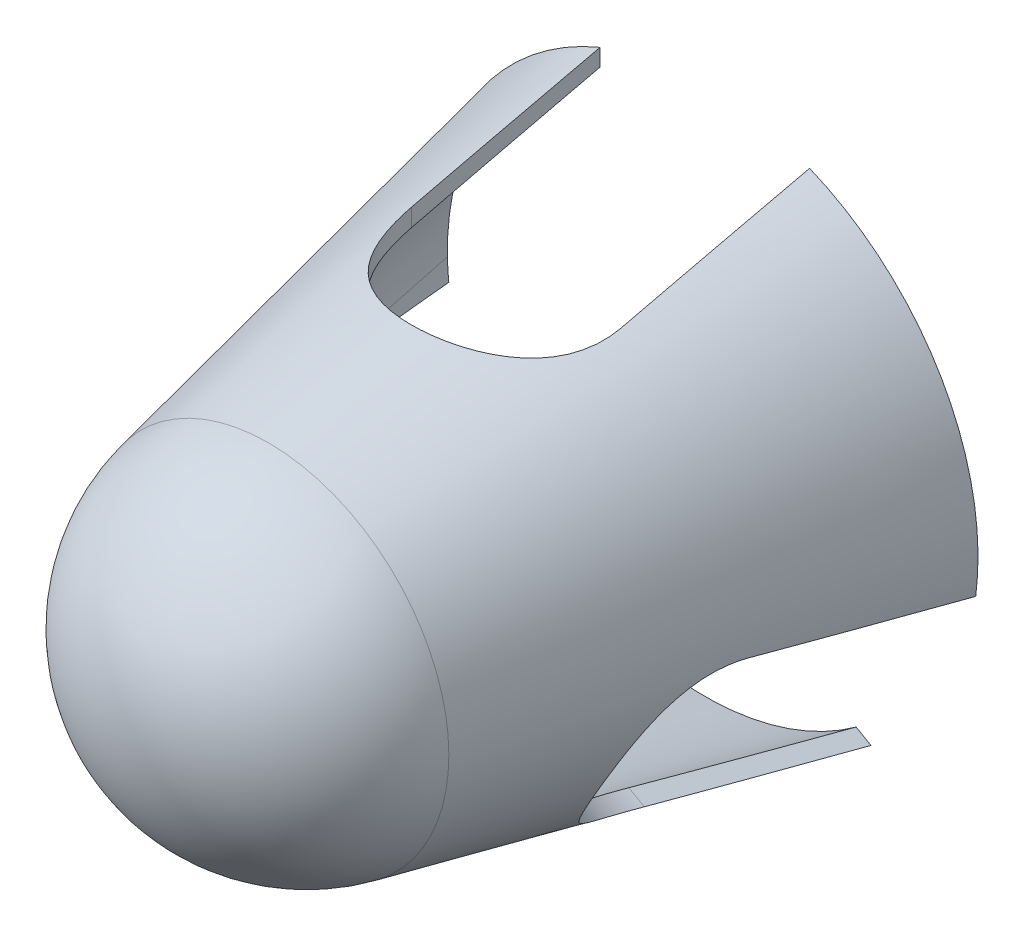
SolidWorks part; units mm, degrees
ref_plane "Ebene vorne" through (0, 0, 0) normal (0, 0, 1) x (1, 0, 0)
ref_plane "Ebene oben" through (0, 0, 0) normal (0, 1, 0) x (1, 0, 0)
ref_plane "Ebene rechts" through (0, 0, 0) normal (1, 0, 0) x (0, 0, -1)
sketch "Skizze1" plane through (0, 0, 0) normal (1, 0, 0) x (0, 0, -1)
  line L0 (900, -1303.8575) -> (900, 0) construction
  line L1 (-1000, 750) -> (1000, 750) construction
  line L2 (-1000, 750) -> (-1000, -750) construction
  line L3 (-1000, -750) -> (1000, -750) construction
  line L4 (1000, 750) -> (1000, -750) construction
  line L6 (900, -1303.8575) -> (-1183.0315, -861.0955)
  line L7 (-1000, 0) -> (-1000, -825)
  line L8 (-1000, -825) -> (900, -1228.8575)
  line L9 (0, 0) -> (-1960.7907, 0) construction
  line L10 (0, 0) -> (4818.5589, 0) construction
  line L11 (-1880.3328, 0) -> (-1000, 0)
  line L12 (900, -1228.8575) -> (900, -1303.8575)
  arc A1 (-1183.0315, -861.0955) -> (-1880.3328, 0) centre (-1000, 0) cw
  point P8 (0, 750)
  point P16 (1000, 0)
  dimension "D1" = 2000
  dimension "D2" = 1500
  dimension "D3" = 75
  dimension "D6" = 75
  dimension "D7" = 12
  dimension "D8" = 100
  dimension "D9" = 12
revolve "Rotation1" add sketch "Skizze1" angle 360 about L10
sketch "Skizze2" plane through (0, 0, 0) normal (0, 1, 0) x (1, 0, 0)
  line L0 (-500, 0) -> (-500, 900)
  line L1 (1228.8575, 900) -> (-1228.8575, 900) construction
  line L2 (-500, 900) -> (500, 900)
  line L3 (500, 900) -> (500, 0)
  arc A1 (-500, 0) -> (500, 0) centre (0, 0) ccw
  dimension "D1" = 500
extrude "Schnitt-Linear austragen1" cut sketch "Skizze2" along normal through all contours L2 L3 A1 L0
pattern_circular "Kreismuster1" count 3 over 360 about axis through (0, 0, 1000) along (0, 0, -1) of "Schnitt-Linear austragen1" reverse direction yes
